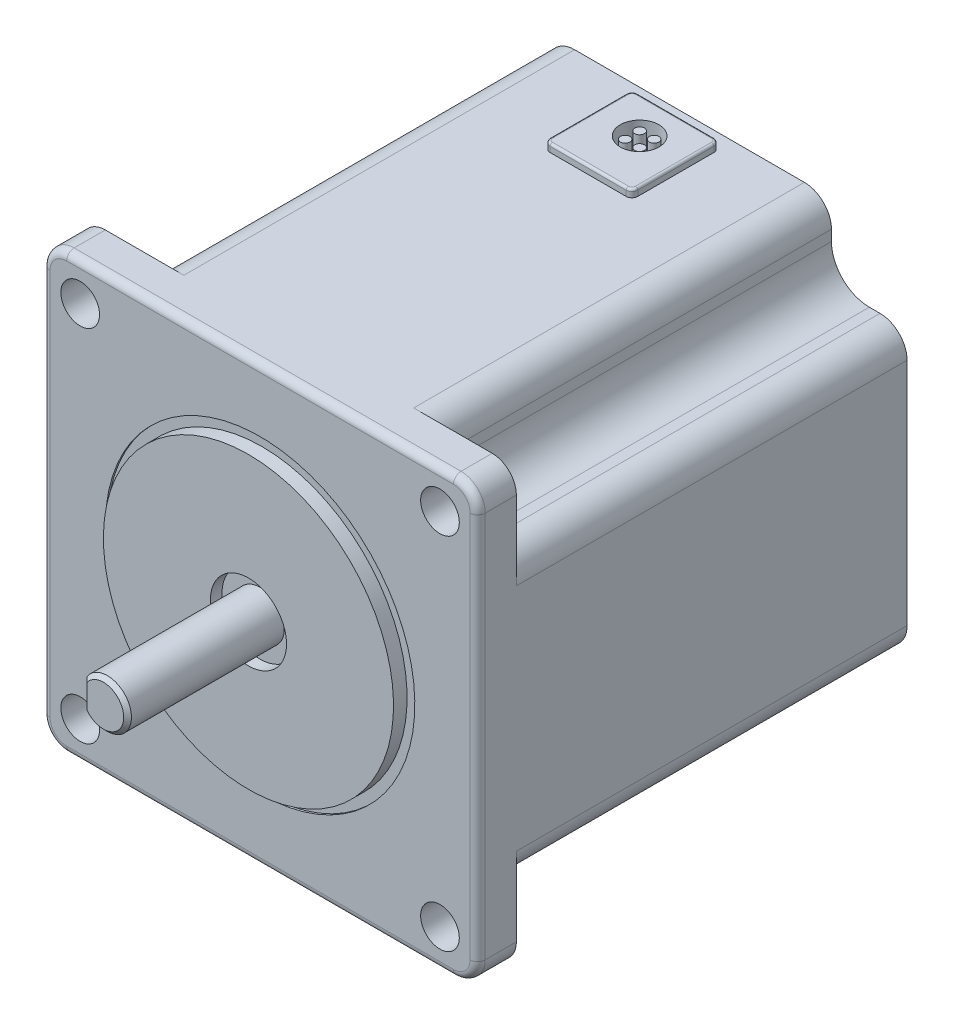
SolidWorks part; units mm, degrees
ref_plane "Front Plane" through (0, 0, 0) normal (0, 0, 1) x (1, 0, 0)
ref_plane "Top Plane" through (0, 0, 0) normal (0, 1, 0) x (1, 0, 0)
ref_plane "Right Plane" through (0, 0, 0) normal (1, 0, 0) x (0, 0, -1)
sketch "Sketch1" plane through (0, 0, 0) normal (0, 0, 1) x (1, 0, 0)
  line L0 (-2.667, -1.7227) -> (-2.667, 1.7227) construction
  line L1 (28.575, -28.575) -> (-28.575, -28.575) construction
  line L2 (28.575, -28.575) -> (28.575, 28.575) construction
  line L3 (28.575, 28.575) -> (-28.575, 28.575) construction
  line L4 (-28.575, -28.575) -> (-28.575, 28.575) construction
  line L5 (28.575, -28.575) -> (-28.575, 28.575) construction
  line L6 (28.575, 28.575) -> (-28.575, -28.575) construction
  line L7 (23.622, -23.622) -> (-23.622, -23.622) construction
  line L8 (23.622, -23.622) -> (23.622, 23.622) construction
  line L9 (23.622, 23.622) -> (-23.622, 23.622) construction
  line L10 (-23.622, -23.622) -> (-23.622, 23.622) construction
  line L11 (23.622, -23.622) -> (-23.622, 23.622) construction
  line L12 (23.622, 23.622) -> (-23.622, -23.622) construction
  circle A0 centre (-23.622, 23.622) radius 2.54 construction
  circle A1 centre (23.622, 23.622) radius 2.54 construction
  circle A2 centre (-23.622, -23.622) radius 2.54 construction
  circle A3 centre (23.622, -23.622) radius 2.54 construction
  circle A4 centre (0, 0) radius 3.175 construction
  circle A5 centre (0, 0) radius 19.05 construction
  point P0 (0, 0)
  point P6 (0, 0)
  point P18 (0, 3.175)
  point P19 (0, 28.575)
  point P20 (0, 19.05)
  point P21 (-23.622, -26.162)
  dimension "D3" = 5.08
  dimension "D4" = 6.35
  dimension "D5" = 38.1
  dimension "D1" = 57.15
  dimension "D2" = 47.244
  dimension "D6" = 5.842
sketch "Sketch2" plane through (0, 0, 0) normal (1, 0, 0) x (0, 0, -1)
  line L0 (0, 0) -> (56.388, 0) construction
  line L1 (0, 0) -> (-20.574, 0) construction
  line L2 (-20.574, -3.175) -> (-20.574, 3.175) construction
  line L3 (56.388, -28.575) -> (56.388, 28.575) construction
  line L4 (0, 28.575) -> (0, -28.575) construction
  line L5 (-1.524, 19.05) -> (-1.524, -19.05) construction
  line L6 (5.08, 28.575) -> (5.08, -28.575) construction
  point P3 (-1.524, 0)
  point P18 (5.08, 0)
  point P19 (-5.588, 0)
  dimension "D1" = 20.574
  dimension "A" = 56.388
  dimension "D2" = 1.524
  dimension "D3" = 5.08
  dimension "D4" = 14.986
sketch "Sketch3" plane through (0, 0, 0) normal (0, 0, 1) x (1, 0, 0)
  line L1 (-28.575, -28.575) -> (-28.575, 28.575) construction
  line L2 (28.575, 28.575) -> (-28.575, 28.575) construction
  line L3 (28.575, -28.575) -> (28.575, 28.575) construction
  line L4 (28.575, -28.575) -> (-28.575, -28.575) construction
  line L5 (-28.575, -25.4) -> (-28.575, 25.4)
  line L6 (25.4, 28.575) -> (-25.4, 28.575)
  line L7 (28.575, -25.4) -> (28.575, 25.4)
  line L8 (25.4, -28.575) -> (-25.4, -28.575)
  arc A4 (-28.575, 25.4) -> (-25.4, 28.575) centre (-25.4, 25.4) cw
  arc A5 (25.4, 28.575) -> (28.575, 25.4) centre (25.4, 25.4) cw
  arc A6 (28.575, -25.4) -> (25.4, -28.575) centre (25.4, -25.4) cw
  arc A7 (-25.4, -28.575) -> (-28.575, -25.4) centre (-25.4, -25.4) cw
  dimension "D1" = 3.175
extrude "Boss-Extrude1" add sketch "Sketch3" against normal up to vertex (5.08 mm away) up to point (0, 0, -5.08)
fillet "Fillet1" radius 0.9906 8 edges at (0, 28.575, 0) (28.575, 0, 0) (0, -28.575, 0) (-28.575, 0, 0) (27.6451, 27.6451, 0) (27.6451, -27.6451, 0) (-27.6451, -27.6451, 0) (-27.6451, 27.6451, 0)
sketch "Sketch4" plane through (0, 0, -5.08) normal (0, 0, 1) x (1, 0, 0)
  line L0 (0, 28.575) -> (0, 0) construction
  line L1 (0, 0) -> (-28.575, 0) construction
  line L2 (-25.019, 18.6436) -> (-23.622, 18.6436)
  line L3 (-18.6436, 23.622) -> (-18.6436, 25.019)
  line L4 (-28.575, 25.4) -> (-28.575, -25.4)
  line L5 (25.4, 28.575) -> (-25.4, 28.575)
  line L6 (28.575, -25.4) -> (28.575, 25.4)
  line L7 (-25.4, -28.575) -> (25.4, -28.575)
  line L8 (-28.575, 15.0876) -> (-28.575, -15.0876)
  line L9 (15.0876, 28.575) -> (-15.0876, 28.575)
  line L10 (28.575, -15.0876) -> (28.575, 15.0876)
  line L14 (28.575, 28.575) -> (-28.575, 28.575) construction
  line L15 (18.6436, 23.622) -> (18.6436, 25.019)
  line L16 (25.019, 18.6436) -> (23.622, 18.6436)
  line L17 (25.019, -18.6436) -> (23.622, -18.6436)
  line L18 (18.6436, -23.622) -> (18.6436, -25.019)
  line L19 (15.0876, -28.575) -> (-15.0876, -28.575)
  line L20 (-18.6436, -23.622) -> (-18.6436, -25.019)
  line L21 (-25.019, -18.6436) -> (-23.622, -18.6436)
  arc A0 (-25.019, 18.6436) -> (-28.575, 15.0876) centre (-25.019, 15.0876) ccw
  arc A1 (-15.0876, 28.575) -> (-18.6436, 25.019) centre (-15.0876, 25.019) ccw
  arc A2 (-23.622, 18.6436) -> (-18.6436, 23.622) centre (-23.622, 23.622) ccw
  arc A3 (23.622, 18.6436) -> (18.6436, 23.622) centre (23.622, 23.622) cw
  arc A4 (-25.4, 28.575) -> (-28.575, 25.4) centre (-25.4, 25.4) ccw
  arc A5 (15.0876, 28.575) -> (18.6436, 25.019) centre (15.0876, 25.019) cw
  arc A6 (28.575, 25.4) -> (25.4, 28.575) centre (25.4, 25.4) ccw
  arc A7 (25.019, 18.6436) -> (28.575, 15.0876) centre (25.019, 15.0876) cw
  arc A8 (25.4, -28.575) -> (28.575, -25.4) centre (25.4, -25.4) ccw
  arc A10 (-28.575, -25.4) -> (-25.4, -28.575) centre (-25.4, -25.4) ccw
  arc A11 (25.019, -18.6436) -> (28.575, -15.0876) centre (25.019, -15.0876) ccw
  arc A12 (15.0876, -28.575) -> (18.6436, -25.019) centre (15.0876, -25.019) ccw
  arc A13 (23.622, -18.6436) -> (18.6436, -23.622) centre (23.622, -23.622) ccw
  arc A14 (-23.622, -18.6436) -> (-18.6436, -23.622) centre (-23.622, -23.622) cw
  arc A15 (-15.0876, -28.575) -> (-18.6436, -25.019) centre (-15.0876, -25.019) cw
  arc A16 (-25.019, -18.6436) -> (-28.575, -15.0876) centre (-25.019, -15.0876) cw
  dimension "D2" = 4.9784
  dimension "D3" = 3.556
  dimension "D1" = 0
extrude "Boss-Extrude2" add sketch "Sketch4" against normal up to vertex (51.308 mm away) up to point (0, 0, -56.388)
sketch "Sketch5" plane through (0, 0, 0) normal (1, 0, 0) x (0, 0, -1)
  line L1 (0, 0) -> (-1.524, 0)
  line L2 (0, 0) -> (0, 19.05)
  line L3 (0, 19.05) -> (-1.524, 19.05)
  line L4 (-1.524, 0) -> (-1.524, 19.05)
revolve "Revolve1" add sketch "Sketch5" angle 360 about L1
sketch "Sketch6" plane through (0, 0, 0) normal (1, 0, 0) x (0, 0, -1)
  line L0 (-20.574, 0) -> (-1.524, 0) construction
  line L1 (56.388, 0) -> (-1.524, 0)
  line L2 (56.388, 0) -> (56.388, 3.175)
  line L3 (0, 5) -> (-1.524, 5)
  line L4 (-1.524, 0) -> (-1.524, 5)
  line L5 (56.388, 3.175) -> (0, 3.175)
  line L6 (0, 3.175) -> (0, 5)
  line L10 (0, 20.32) -> (0.254, 20.32)
  line L11 (0, 20.32) -> (0, 19.05)
  line L12 (0, 19.05) -> (0.254, 19.05)
  line L13 (0.254, 20.32) -> (0.254, 19.05)
  dimension "D1" = 10
  dimension "D2" = 40.64
  dimension "D3" = 0.254
revolve "Cut-Revolve1" cut sketch "Sketch6" angle 360 about L0
sketch "Sketch7" plane through (0, 0, 0) normal (1, 0, 0) x (0, 0, -1)
  line L1 (-20.574, 3.175) -> (56.388, 3.175)
  line L2 (-20.574, 3.175) -> (-20.574, 0)
  line L3 (-20.574, 0) -> (56.388, 0)
  line L4 (56.388, 3.175) -> (56.388, 0)
revolve "Revolve2" add sketch "Sketch7" angle 360 about L3
sketch "Sketch8" plane through (0, 0, 20.574) normal (0, 0, 1) x (1, 0, 0)
  line L0 (-2.667, -1.7227) -> (-2.667, 1.7227) construction
  line L1 (-2.667, -1.7227) -> (-2.667, 1.7227)
  circle A0 centre (0, 0) radius 3.175 construction
  arc A1 (-2.667, 1.7227) -> (-2.667, -1.7227) centre (0, 0) ccw
extrude "Cut-Extrude1" cut sketch "Sketch8" against normal up to vertex (14.986 mm away) up to point (0, 0, 5.588)
chamfer "Chamfer1" distance 0.508 angle 45 3 edges at (0, -3.175, -56.388) (3.175, 0, 20.574) (-2.667, 0, 20.574)
sketch "Sketch9" plane through (0, 0, 0) normal (0, 0, 1) x (1, 0, 0)
  circle A0 centre (23.622, -23.622) radius 2.54 construction
  circle A1 centre (23.622, -23.622) radius 2.54
  circle A2 centre (-23.622, -23.622) radius 2.54 construction
  circle A3 centre (-23.622, 23.622) radius 2.54 construction
  circle A4 centre (23.622, 23.622) radius 2.54 construction
  circle A5 centre (-23.622, -23.622) radius 2.54
  circle A6 centre (-23.622, 23.622) radius 2.54
  circle A7 centre (23.622, 23.622) radius 2.54
extrude "Cut-Extrude2" cut sketch "Sketch9" against normal up to next (5.08 mm away)
sketch "Sketch10" plane through (0, 28.575, -0.7512) normal (0, 1, 0) x (1, 0, 0)
  line L0 (0, -0.7512) -> (0, 49.0887) construction
  line L2 (-3.8354, 49.0887) -> (-3.8354, 44.1357)
  line L3 (-3.8354, 44.1357) -> (3.8354, 44.1357)
  line L4 (3.8354, 49.0887) -> (3.8354, 44.1357)
  line L5 (25.4, -0.7512) -> (-25.4, -0.7512) construction
  line L7 (15.0876, 55.6368) -> (-15.0876, 55.6368) construction
  arc A0 (3.8354, 49.0887) -> (-3.8354, 49.0887) centre (0, 49.0887) ccw
  dimension "D1" = 7.6708
  dimension "D2" = 4.953
  dimension "D3" = 6.5481
extrude "Cut-Extrude3" cut sketch "Sketch10" against normal blind 1.2954
sketch "Sketch11" plane through (0, 27.2796, 0) normal (0, 1, 0) x (1, 0, 0)
  circle A0 centre (0, 49.8399) radius 2.54
  circle A1 centre (0, 49.8399) radius 3.7465
  dimension "D1" = 5.08
  dimension "D2" = 7.493
extrude "Boss-Extrude3" add sketch "Sketch11" along normal up to surface (1.2954 mm away) up to face at (0, 28.575, -48.3222)
sketch "Sketch12" plane through (0, 28.575, 0) normal (0, 1, 0) x (1, 0, 0)
  line L0 (0, 48.8366) -> (0, 0) construction
  line L1 (-5.7531, 43.0835) -> (5.7531, 43.0835)
  line L2 (-5.7531, 43.0835) -> (-5.7531, 54.5897)
  line L3 (-5.7531, 54.5897) -> (5.7531, 54.5897)
  line L4 (5.7531, 43.0835) -> (5.7531, 54.5897)
  line L5 (-5.7531, 43.0835) -> (5.7531, 54.5897) construction
  line L6 (-5.7531, 54.5897) -> (5.7531, 43.0835) construction
  circle A2 centre (0, 49.8399) radius 2.54 construction
  circle A3 centre (0, 49.8399) radius 2.54
  point P0 (0, 48.8366)
  dimension "D2" = 4.7498
  dimension "D1" = 11.5062
extrude "Boss-Extrude4" add sketch "Sketch12" along normal blind 1.016
fillet "Fillet2" radius 0.762 4 edges at (5.7531, 29.083, -54.5897) (-5.7531, 29.083, -54.5897) (5.7531, 29.083, -43.0835) (-5.7531, 29.083, -43.0835)
fillet "Fillet3" radius 0.3048 8 edges at (-5.5299, 29.591, -43.3067) (-5.7531, 29.591, -48.8366) (-5.5299, 29.591, -54.3665) (0, 29.591, -54.5897) (5.5299, 29.591, -54.3665) (5.7531, 29.591, -48.8366) (5.5299, 29.591, -43.3067) (0, 29.591, -43.0835)
sketch "Sketch13" plane through (0, 27.2796, 0) normal (0, 1, 0) x (1, 0, 0)
  line L4 (-0.9525, 48.8874) -> (0.9525, 48.8874) construction
  line L5 (-0.9525, 48.8874) -> (-0.9525, 50.7924) construction
  line L6 (-0.9525, 50.7924) -> (0.9525, 50.7924) construction
  line L7 (0.9525, 48.8874) -> (0.9525, 50.7924) construction
  line L8 (-0.9525, 48.8874) -> (0.9525, 50.7924) construction
  line L9 (-0.9525, 50.7924) -> (0.9525, 48.8874) construction
  circle A0 centre (-0.9525, 50.7924) radius 0.635
  circle A1 centre (0.9525, 50.7924) radius 0.635
  circle A2 centre (0.9525, 48.8874) radius 0.635
  circle A3 centre (-0.9525, 48.8874) radius 0.635
  circle A4 centre (0, 49.8399) radius 2.54 construction
  point P8 (0, 49.8399)
  dimension "D1" = 1.27
  dimension "D2" = 1.905
extrude "Boss-Extrude5" add sketch "Sketch13" along normal blind 1.9304
